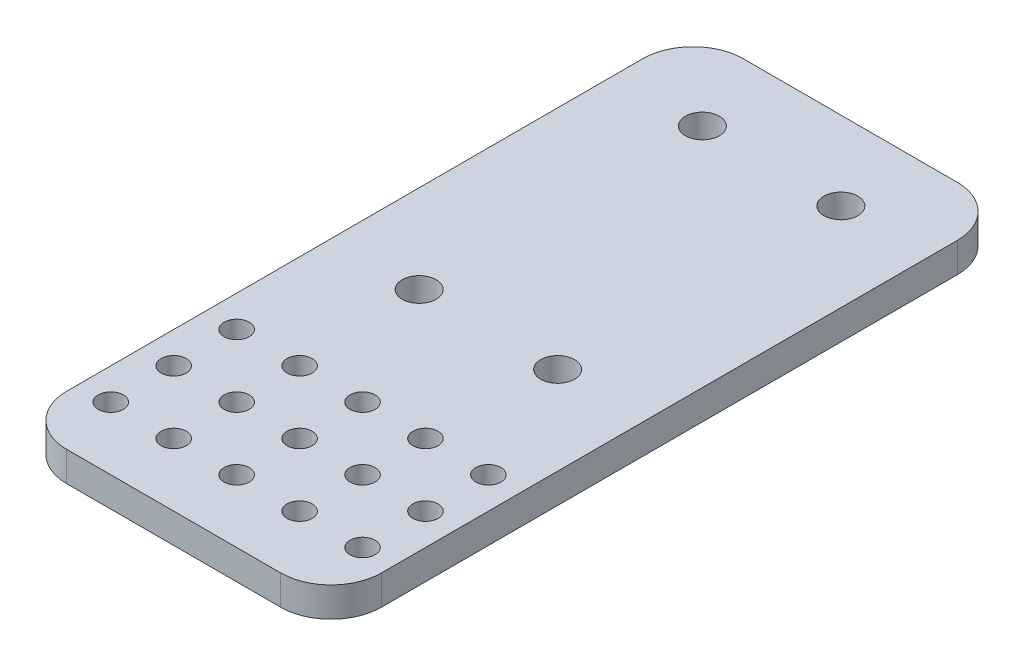
SolidWorks part; units mm, degrees
other "Markup1"
sketch "Sketch3" plane through (0, 6, 0) normal (-0.2556, 0.7181, 0.6473) x (0.9665, 0.2047, 0.1545)
sketch "Sketch5" plane through (0, 6, 0) normal (-0.2556, 0.7181, 0.6473) x (0.9665, 0.2047, 0.1545)
ref_plane "Front Plane" through (0, 0, 0) normal (0, 0, 1) x (1, 0, 0)
ref_plane "Top Plane" through (0, 0, 0) normal (0, 1, 0) x (1, 0, 0)
ref_plane "Right Plane" through (0, 0, 0) normal (1, 0, 0) x (0, 0, -1)
sketch "Sketch1" plane through (0, 0, 0) normal (0, 1, 0) x (1, 0, 0)
  line L0 (31.75, 136.525) -> (31.75, 0) construction
  line L1 (0, 0) -> (63.5, 0)
  line L2 (0, 0) -> (0, 136.525)
  line L3 (0, 136.525) -> (63.5, 136.525)
  line L4 (63.5, 0) -> (63.5, 136.525)
  line L5 (57.15, 12.7) -> (44.45, 12.7) construction
  line L6 (57.15, 12.7) -> (57.15, 25.4) construction
  circle A0 centre (17.78, 120.65) radius 3.429 construction
  circle A1 centre (45.72, 63.5) radius 3.429 construction
  circle A2 centre (17.78, 63.5) radius 3.429 construction
  circle A3 centre (45.72, 120.65) radius 3.429 construction
  circle A4 centre (57.15, 12.7) radius 2.54
  circle A5 centre (44.45, 12.7) radius 2.54
  circle A6 centre (31.75, 12.7) radius 2.54
  circle A7 centre (19.05, 12.7) radius 2.54
  circle A8 centre (44.45, 25.4) radius 2.54
  circle A9 centre (31.75, 25.4) radius 2.54
  circle A10 centre (19.05, 25.4) radius 2.54
  circle A11 centre (44.45, 38.1) radius 2.54
  circle A12 centre (31.75, 38.1) radius 2.54
  circle A13 centre (19.05, 38.1) radius 2.54
  circle A14 centre (57.15, 25.4) radius 2.54
  circle A15 centre (57.15, 38.1) radius 2.54
  circle A16 centre (6.35, 12.7) radius 2.54
  circle A17 centre (6.35, 25.4) radius 2.54
  circle A18 centre (6.35, 38.1) radius 2.54
  dimension "D3" = 57.15
  dimension "D4" = 27.94
  dimension "D5" = 6.858
  dimension "D6" = 15.875
  dimension "D7" = 17.78
  dimension "D8" = 12.7
  dimension "D9" = 6.35
  dimension "D10" = 5.08
  dimension "D2" = 25.4
  dimension "D1" = 63.5
  dimension "D13" = 12.7
  dimension "D14" = 12.7
  dimension "D11" = 5
  dimension "D12" = 3
extrude "Boss-Extrude1" add sketch "Sketch1" along normal blind 6 contours L4 L3 L2 region at (31.75, 0, -69.8203)
fillet "Fillet1" radius 10.16 4 edges at (0, 3, -136.525) (63.5, 3, -136.525) (63.5, 3, 0) (0, 3, 0)
sketch "Sketch6" plane through (0, 6, 0) normal (0, 1, 0) x (1, 0, 0)
  circle A0 centre (17.78, 120.65) radius 3.429 construction
  circle A1 centre (45.72, 120.65) radius 3.429 construction
  circle A2 centre (17.78, 63.5) radius 3.429 construction
  circle A3 centre (45.72, 63.5) radius 3.429 construction
  circle A4 centre (17.78, 120.65) radius 3.429
  circle A5 centre (45.72, 120.65) radius 3.429
  circle A6 centre (17.78, 63.5) radius 3.429
  circle A7 centre (45.72, 63.5) radius 3.429
extrude "Cut-Extrude2" cut sketch "Sketch6" against normal through all
sketch "Sketch4" plane through (0, 0, 0) normal (0, -1, 0) x (-1, 0, 0)
  line L1 (-63.5, 10.16) -> (-63.5, 126.365) construction
  line L2 (-63.5, -1000) -> (-63.5, 49000) construction
  line L4 (-1076.9756, 0) -> (48923.0244, 0) construction
  line L6 (-10.16, 0) -> (-53.34, 0) construction
  point P6 (-63.5, 0)
